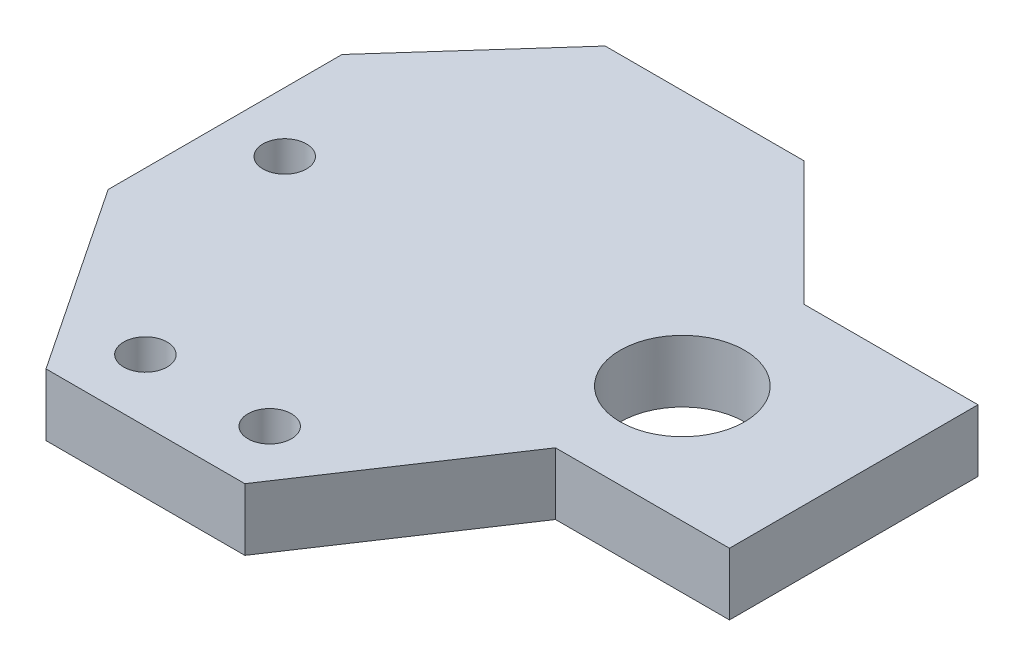
SolidWorks part; units mm, degrees
ref_plane "Front Plane" through (0, 0, 0) normal (0, 0, 1) x (1, 0, 0)
ref_plane "Top Plane" through (0, 0, 0) normal (0, 1, 0) x (1, 0, 0)
ref_plane "Right Plane" through (0, 0, 0) normal (1, 0, 0) x (0, 0, -1)
sketch "Sketch1" plane through (0, 0, 0) normal (0, 1, 0) x (1, 0, 0)
  line L0 (0, 33.8197) -> (10, 45)
  line L1 (0, 0) -> (50, 0)
  line L2 (0, 0) -> (0, 45)
  line L3 (0, 45) -> (50, 45)
  line L4 (50, 0) -> (50, 45)
  line L5 (0, 15) -> (10, 0)
  line L6 (26, 45) -> (36, 35)
  line L7 (26, 0) -> (36, 15)
  line L8 (36, 15) -> (50, 15)
  line L9 (36, 35) -> (50, 35)
  line L10 (50, 25) -> (0, 25) construction
  circle A1 centre (13, 5) radius 1.75
  circle A2 centre (23, 5) radius 1.75
  dimension "D15" = 10
  dimension "D16" = 3.5
  dimension "D24" = 3
  dimension "D25" = 3
  dimension "D17" = 3.5
  dimension "D1" = 45
  dimension "D2" = 50
  dimension "D3" = 15
  dimension "D4" = 10
  dimension "D5" = 10
  dimension "D6" = 15
  dimension "D7" = 16
  dimension "D8" = 16
  dimension "D9" = 10
  dimension "D10" = 10
  dimension "D11" = 10
  dimension "D12" = 20
  dimension "D13" = 10
  dimension "D18" = 5
extrude "Boss-Extrude1" add sketch "Sketch1" along normal blind 5 contours L4 L10 L2 L5 L1 L7 L8 | L10 L4 L9 L6 L3 L0 L2 | L10 | L10 region at (22.3613, 0, -23.5179)
ref_plane "Plane1" through (0, 0, 0) normal (0, -1, 0) x (-1, 0, 0)
sketch "Sketch2" plane through (0, 0, 0) normal (0, -1, 0) x (-1, 0, 0)
  line L0 (0, 24.4098) -> (-68.9029, 24.4098) construction
  line L1 (0, 15) -> (0, 33.8197) construction
  circle A0 centre (-4.8, 24.4098) radius 1.75
  circle A1 centre (-36.8, 24.4098) radius 5
  dimension "D1" = 4.8
  dimension "D2" = 10
  dimension "D3" = 32
extrude "Cut-Extrude1" cut sketch "Sketch2" against normal blind 10
